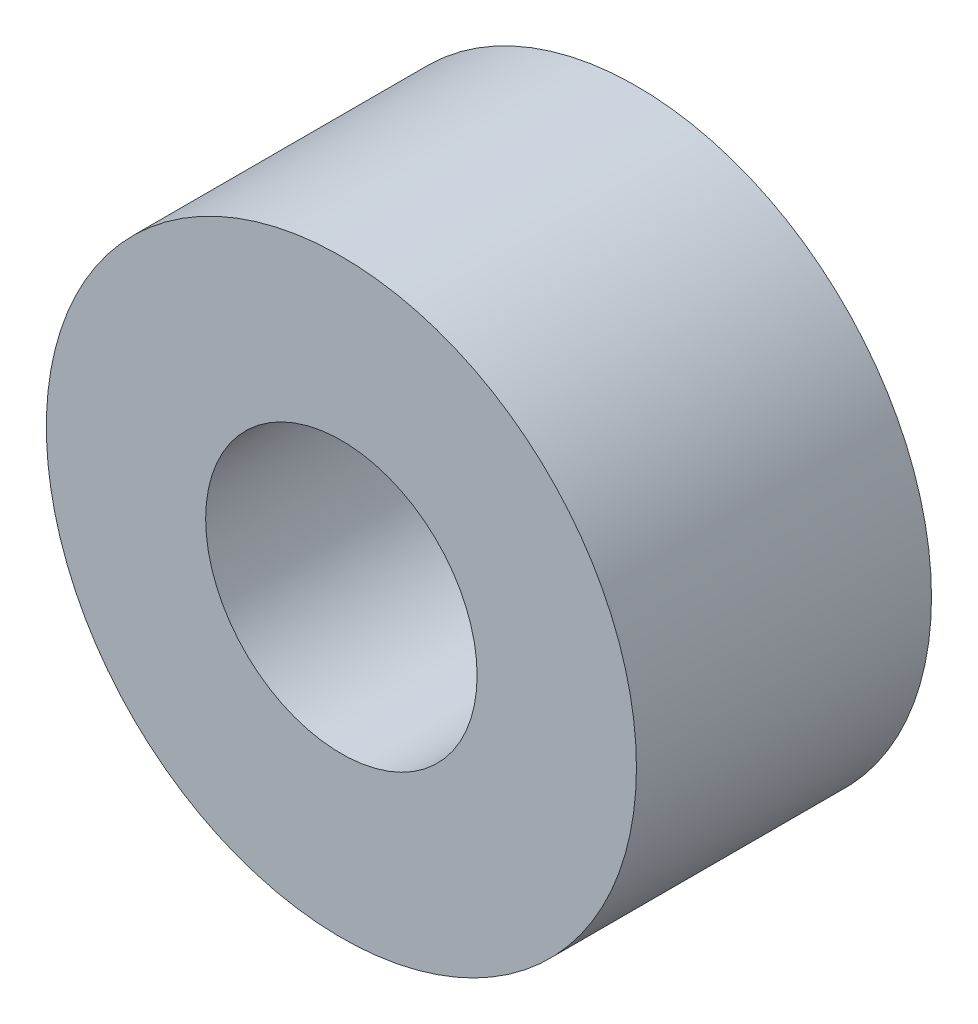
SolidWorks part; units mm, degrees
material "ABS"
ref_plane "Front Plane" through (0, 0, 0) normal (0, 0, 1) x (1, 0, 0)
ref_plane "Top Plane" through (0, 0, 0) normal (0, 1, 0) x (1, 0, 0)
ref_plane "Right Plane" through (0, 0, 0) normal (1, 0, 0) x (0, 0, -1)
sketch "Sketch1" plane through (0, 0, 0) normal (0, 0, 1) x (1, 0, 0)
  circle A0 centre (0, 0) radius 3.175
  circle A1 centre (0, 0) radius 1.4605
  dimension "OD" = 6.35
  dimension "ID" = 2.921
extrude "Extrude1" add sketch "Sketch1" along normal mid plane 3.175
sketch "Sketch2" plane through (0, 0, 0) normal (1, 0, 0) x (0, 0, -1)
  line L0 (-1.5875, -1.4605) -> (1.5875, -1.4605) construction
  line L3 (1.5875, 1.4605) -> (-1.5875, 1.4605) construction
  line L5 (-1.5875, -1.4605) -> (1.5875, -1.4605)
  line L6 (1.5875, 1.4605) -> (-1.5875, 1.4605)
sketch "Sketch4" plane through (0, 0, 1.5875) normal (0, 0, 1) x (1, 0, 0)
  line L0 (0, 0) -> (-1.0327, 1.0327)
  line L1 (0, -2.1828) -> (0, 2.1828) construction
  circle A0 centre (0, 0) radius 1.4605 construction
  dimension "D1" = 45
